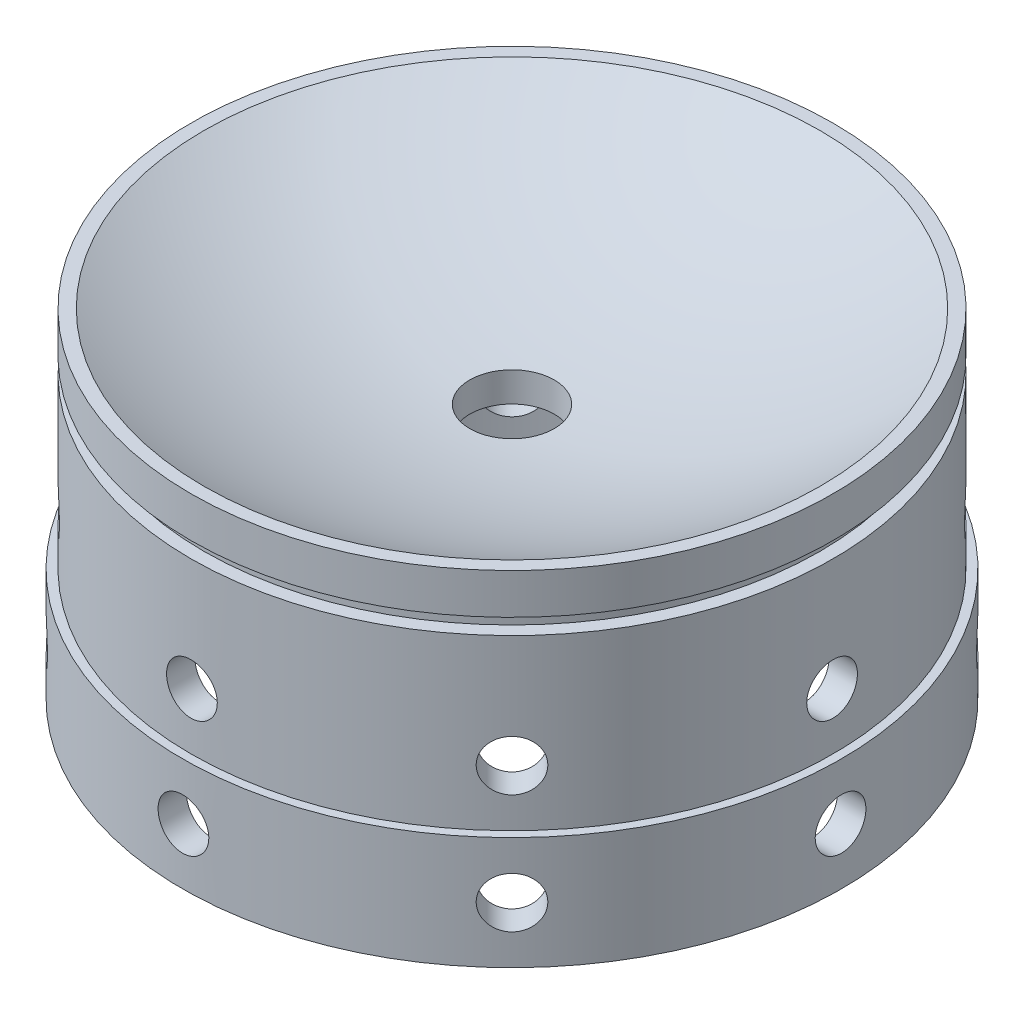
SolidWorks part; units mm, degrees
ref_plane "Front Plane" through (0, 0, 0) normal (0, 0, 1) x (1, 0, 0)
ref_plane "Top Plane" through (0, 0, 0) normal (0, 1, 0) x (1, 0, 0)
ref_plane "Right Plane" through (0, 0, 0) normal (1, 0, 0) x (0, 0, -1)
sketch "Sketch1" plane through (0, 0, 0) normal (0, 0, 1) x (1, 0, 0)
  line L0 (0, 0) -> (0, 6.35)
  line L1 (0, 0) -> (72.39, 0)
  line L2 (72.39, 0) -> (72.39, 12.7)
  line L3 (72.39, 12.7) -> (69.469, 12.7)
  line L4 (69.469, 12.7) -> (69.469, 16.256)
  line L5 (69.469, 16.256) -> (72.39, 16.256)
  line L6 (72.39, 16.256) -> (72.39, 25.4)
  line L7 (72.39, 25.4) -> (69.469, 25.4)
  line L8 (69.469, 25.4) -> (69.469, 6.35) construction
  line L9 (69.469, 6.35) -> (0, 6.35) construction
  line L10 (72.39, 0) -> (72.39, -25.4)
  line L11 (72.39, -25.4) -> (66.04, -25.4)
  line L12 (66.04, -25.4) -> (66.04, 0)
  line L13 (74.93, 68.1653) -> (74.93, 53.6699) construction
  line L14 (67.945, -50.8) -> (67.945, -25.4)
  line L15 (67.945, -50.8) -> (74.295, -50.8)
  line L16 (9.525, 6.6835) -> (9.525, 0)
  line L17 (73.025, 45.3691) -> (73.025, 21.7883) construction
  line L18 (74.295, -50.8) -> (74.295, -25.4)
  line L19 (74.295, -25.4) -> (72.39, -25.4)
  arc A0 (69.469, 25.4) -> (0, 6.35) centre (0, 142.5401) cw
  dimension "D1" = 72.39
  dimension "D5" = 25.4
  dimension "D9" = 6.35
  dimension "D12" = 9.525
  dimension "D3" = 12.7
  dimension "D4" = 3.556
  dimension "D2" = 73.025
  dimension "D13" = 3.556
  dimension "D6" = 6.35
  dimension "D7" = 25.4
  dimension "D8" = 74.93
  dimension "D10" = 25.4
  dimension "D11" = 74.295
revolve "Revolve1" add sketch "Sketch1" angle 360 about L0 region at (48.1528, 8.1766, 0) region at (69.215, -12.7, 0) region at (71.12, -38.1, 0)
hole_wizard "1/2 (0.45) Diameter Hole3" positions "3DSketch5" profile "Sketch8" hole size "1/2" standard "ANSI Inch"
sketch3d "3DSketch5"
  line L0 (0, -25.4, 0) -> (0, 0, 0) construction
  line L2 (0, -12.7, 0) -> (72.39, -12.7, 0)
  circle A8 centre (0, -25.4, 0) radius 72.39 construction
  circle A9 centre (0, -25.4, 0) radius 72.39
  point P0 (72.39, -12.7, 0)
  point P41 (0, -97.79, 0)
  point P43 (0, -97.79, 0)
  point P53 (72.39, -12.7, 0)
  point P62 (0, 0, 0)
sketch "Sketch8" plane through (72.39, -12.7, 0) normal (0, 1, 0) x (0, 0, -1)
  line L0 (0, 0) -> (0, 75.8229)
  line L1 (0, 75.8229) -> (5.715, 72.389)
  line L2 (5.715, 72.389) -> (5.715, 0)
  line L5 (5.715, 0) -> (0, 0)
  line L10 (0, 75.8229) -> (-5.715, 72.389) construction
  line L11 (0, -6.35) -> (0, 107.95) construction
  dimension "Hole Dia." = 11.43
  dimension "Hole Depth" = 72.389
  dimension "Drill Angle" = 118
hole_wizard "1/2 (0.45) Diameter Hole2" positions "3DSketch6" profile "Sketch9" hole size "1/2" standard "ANSI Inch"
sketch3d "3DSketch6"
  line L0 (0, -25.4, 0) -> (0, -50.8, 0)
  line L2 (0, -38.1, 0) -> (74.295, -38.1, 0)
  circle A0 centre (0, -50.8, 0) radius 74.295 construction
  circle A1 centre (0, -25.4, 0) radius 74.295 construction
  circle A2 centre (0, -50.8, 0) radius 74.295
  circle A3 centre (0, -25.4, 0) radius 74.295
  point P0 (74.295, -38.1, 0)
  point P5 (0, -125.095, 0)
  point P8 (0, -99.695, 0)
  point P10 (0, -125.095, 0)
  point P12 (0, -99.695, 0)
sketch "Sketch9" plane through (74.295, -38.1, 0) normal (0, 1, 0) x (0, 0, -1)
  line L0 (0, 0) -> (0, 77.7279)
  line L1 (0, 77.7279) -> (5.715, 74.294)
  line L2 (5.715, 74.294) -> (5.715, 0)
  line L5 (5.715, 0) -> (0, 0)
  line L10 (0, 77.7279) -> (-5.715, 74.294) construction
  line L11 (0, -6.35) -> (0, 107.95) construction
  dimension "Hole Dia." = 11.43
  dimension "Hole Depth" = 74.294
  dimension "Drill Angle" = 118
ref_axis "CenterAxis" through (0, 6.6835, 0) along (0, -1, 0)
chamfer "Chamfer1" distance 2.54 angle 45 1 edges at (0, -25.4, -67.945)
pattern_circular "CirPattern1" count 8 over 360 about axis through (0, -25.4, 0) along (0, -1, 0) of "1/2 (0.45) Diameter Hole3", "1/2 (0.45) Diameter Hole2"
equation "\"D1@Sketch1\"=(5.75/2)-(0.025in)"
equation "\"D12@Sketch1\"=0.75/2"
equation "\"D2@Sketch1\"=5.75/2"
equation "\"D8@Sketch1\"=5.9/2"
equation "\"D11@Sketch1\"=5.9/2 - (0.025in)"
